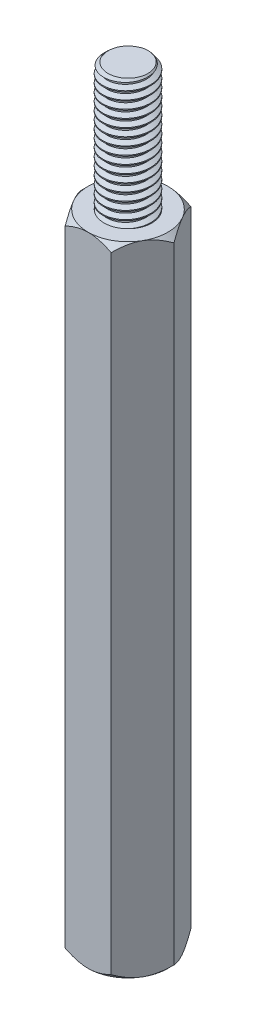
SolidWorks part; units mm, degrees
material "201 Acier inoxydable recuit (SS)"
ref_plane "Plan de face" through (0, 0, 0) normal (0, 0, 1) x (1, 0, 0)
ref_plane "Plan de dessus" through (0, 0, 0) normal (0, 1, 0) x (1, 0, 0)
ref_plane "Plan de droite" through (0, 0, 0) normal (1, 0, 0) x (0, 0, -1)
sketch "Esquisse1" plane through (0, 0, 0) normal (0, 1, 0) x (1, 0, 0)
  line L0 (-4.8113, 0) -> (4.4676, 0) construction
  line L1 (-2.8868, 0) -> (-1.4434, -2.5)
  line L2 (-1.4434, -2.5) -> (1.4434, -2.5)
  line L3 (1.4434, -2.5) -> (2.8868, 0)
  line L4 (2.8868, 0) -> (1.4434, 2.5)
  line L5 (1.4434, 2.5) -> (-1.4434, 2.5)
  line L6 (-1.4434, 2.5) -> (-2.8868, 0)
  line L7 (0, 4.1067) -> (0, -3.6256) construction
  circle A0 centre (0, 0) radius 2.5 construction
  dimension "D1" = 5
extrude "Adjustable height" add sketch "Esquisse1" along normal blind 20 and the other way blind 20
hole_wizard "Trou taraudé M31" positions "Esquisse2" profile "Esquisse3" tap size "M3" standard "ISO"
sketch "Esquisse2" plane through (0, -20, 0) normal (0, -1, 0) x (-1, 0, 0)
  point P0 (0, 0)
cosmetic thread "Filetage de perçage1" parameters "D1"=19.5, "D2"=3
sketch "Esquisse3" plane through (0, -20, 0) normal (1, 0, 0) x (0, 0, -1)
  line L0 (0, 0) -> (0, 20.7511)
  line L1 (0, 20.7511) -> (1.25, 20)
  line L2 (1.25, 20) -> (1.25, 0.5)
  line L3 (1.25, 0.5) -> (1.75, 0)
  line L5 (1.75, 0) -> (0, 0)
  line L6 (-1.25, 0.5) -> (-1.75, 0) construction
  line L10 (0, 20.7511) -> (-1.25, 20) construction
  line L11 (0, -6.35) -> (0, 107.95) construction
  dimension "Diamètre du trou pour taraudage" = 2.5
  dimension "Profondeur du trou pour taraudage" = 20
  dimension "Diamètre du fraisage entrant" = 3.5
  dimension "Angle du fraisage entrant" = 90
  dimension "Angle de pointe" = 118
sketch "Esquisse5" plane through (0, 0, 0) normal (1, 0, 0) x (0, 0, -1)
  line L0 (-2.5, 20) -> (-3.5, 19)
  line L1 (0, 20) -> (0, -20) construction
  line L2 (-3.5, 19) -> (-3.5, 20)
  line L3 (-3.5, 20) -> (-2.5, 20)
  line L4 (0, 23.8266) -> (0, -25.6452) construction
  line L5 (-7.434, 0) -> (6.7788, 0) construction
  line L6 (-3.5, -19) -> (-3.5, -20)
  line L7 (-2.5, -20) -> (-3.5, -19)
  line L8 (-3.5, -20) -> (-2.5, -20)
  dimension "D1" = 45
  dimension "D2" = 1
revolve "Enlèvement de matière-Révolution1" cut sketch "Esquisse5" angle 360 about L4
sketch "Esquisse6" plane through (0, 20, 0) normal (0, 1, 0) x (1, 0, 0)
  circle A0 centre (0, 0) radius 1.5
  dimension "D1" = 3
extrude "Boss.-Extru.1" add sketch "Esquisse6" along normal blind 8
chamfer "Chanfrein1" distance 0.25 angle 45 1 edges at (0, 28, 1.5)
ref_plane "Fond de filetage" through (0, 20.25, 0) normal (0, 1, 0) x (1, 0, 0)
thread "Filetage3" pitch 0.5 method cut profile "Profil de filetage6" start angle 0, offset 1, length 0, pitch 0.5, diameter 3
ref_plane "Plan8" through (-1.5, 28.75, 0) normal (0, 0, 1) x (-1, 0, 0)
sketch "Profil de filetage6" plane through (-1.5, 28.75, 0) normal (0, 0, 1) x (-1, 0, 0)
  line L0 (0, 0) -> (0, 0.5) construction
  line L11 (0, 0) -> (0, 0.4375)
  line L12 (0, 0.4375) -> (-0.2706, 0.2812)
  line L13 (-0.2706, 0.2812) -> (-0.2706, 0.1562)
  line L15 (-0.2706, 0.1562) -> (0, 0)
  line L17 (-0.2706, 0.2187) -> (0, 0.2187) construction
  point P2 (0, 0)
  dimension "Pitch" = 0.5
  dimension "Profile_Angle" = 60
  dimension "Profile_Land" = 0.125
  dimension "Profile_Height" = 0.2706
